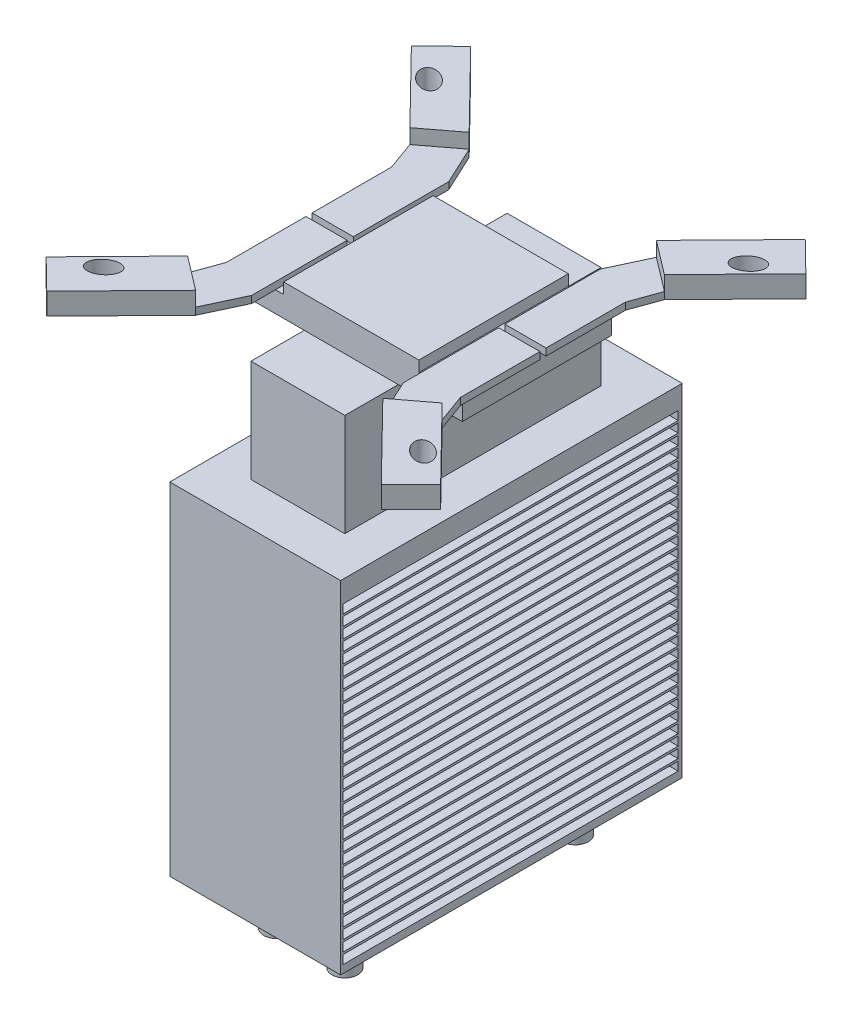
SolidWorks part; units mm, degrees
ref_plane "Front Plane" through (0, 0, 0) normal (0, 0, 1) x (1, 0, 0)
ref_plane "Top Plane" through (0, 0, 0) normal (0, 1, 0) x (1, 0, 0)
ref_plane "Right Plane" through (0, 0, 0) normal (1, 0, 0) x (0, 0, -1)
sketch "Sketch1" plane through (0, 0, 0) normal (0, 1, 0) x (1, 0, 0)
  line L1 (-52.1271, 39.0529) -> (-12.1271, 39.0529)
  line L2 (-52.1271, 39.0529) -> (-52.1271, -40.9471)
  line L3 (-52.1271, -40.9471) -> (-12.1271, -40.9471)
  line L4 (-12.1271, 39.0529) -> (-12.1271, -40.9471)
  dimension "D1" = 40
  dimension "D2" = 80
extrude "Boss-Extrude1" add sketch "Sketch1" along normal blind 80
sketch "Sketch2" plane through (0, 0, 0) normal (0, -1, 0) x (1, 0, 0)
  line L0 (-52.1271, -39.0529) -> (-52.1271, 40.9471) construction
  line L1 (-12.1271, 40.9471) -> (-12.1271, -39.0529) construction
  line L2 (-52.1271, 40.9471) -> (-12.1271, 40.9471) construction
  line L3 (-12.1271, -39.0529) -> (-52.1271, -39.0529) construction
  circle A0 centre (-40.1271, 27.9471) radius 3
  circle A1 centre (-40.1271, -26.0529) radius 3
  circle A2 centre (-24.1271, 27.9471) radius 3
  circle A3 centre (-24.1271, -26.0529) radius 3
  dimension "D1" = 12
  dimension "D2" = 12
  dimension "D3" = 13
  dimension "D4" = 13
  dimension "D5" = 13
  dimension "D6" = 13
  dimension "D7" = 12
  dimension "D8" = 12
extrude "Boss-Extrude2" add sketch "Sketch2" along normal blind 11
sketch "Sketch3" [suppressed] plane through (0, 80, 0) normal (0, 1, 0) x (1, 0, 0)
  line L0 (-12.1271, 39.0529) -> (-52.1271, 39.0529) construction
  line L1 (-52.1271, -40.9471) -> (-12.1271, -40.9471) construction
  line L2 (-52.1271, 39.0529) -> (-52.1271, -40.9471) construction
  line L3 (-12.1271, -40.9471) -> (-12.1271, 39.0529) construction
  circle A0 centre (-40.1271, 26.0529) radius 3
  circle A1 centre (-40.1271, -27.9471) radius 3
  circle A2 centre (-24.1271, 26.0529) radius 3
  circle A3 centre (-24.1271, -27.9471) radius 3
  dimension "D1" = 13
  dimension "D2" = 13
  dimension "D3" = 13
  dimension "D4" = 13
  dimension "D5" = 12
  dimension "D6" = 12
  dimension "D7" = 12
  dimension "D8" = 12
sketch "Sketch7" plane through (0, 80, 0) normal (0, 1, 0) x (1, 0, 0)
  line L1 (-43.1271, 29.0529) -> (-21.1271, 29.0529)
  line L2 (-43.1271, 29.0529) -> (-43.1271, -30.9471)
  line L3 (-43.1271, -30.9471) -> (-21.1271, -30.9471)
  line L4 (-21.1271, 29.0529) -> (-21.1271, -30.9471)
extrude "Boss-Extrude4" add sketch "Sketch7" along normal blind 24
sketch "Sketch8" plane through (0, 104, 0) normal (0, 1, 0) x (1, 0, 0)
  line L1 (-58.1271, 16.5529) -> (-6.1271, 16.5529)
  line L2 (-58.1271, 16.5529) -> (-58.1271, -18.4471)
  line L3 (-58.1271, -18.4471) -> (-6.1271, -18.4471)
  line L4 (-6.1271, 16.5529) -> (-6.1271, -18.4471)
  line L5 (-12.1271, 39.0529) -> (-52.1271, 39.0529) construction
  line L7 (-52.1271, 39.0529) -> (-52.1271, -40.9471) construction
  point P4 (-32.1271, 16.5529)
  point P8 (-58.1271, -0.9471)
  dimension "D1" = 52
  dimension "D2" = 35
  dimension "D3" = 40
  dimension "D4" = 20
extrude "Boss-Extrude5" add sketch "Sketch8" along normal blind 4.86
sketch "Sketch9" plane through (0, 108.86, 0) normal (0, 1, 0) x (1, 0, 0)
  line L0 (-6.1271, 16.5529) -> (-58.1271, 16.5529) construction
  line L1 (-47.9671, 16.5529) -> (-16.2871, 16.5529)
  line L2 (-47.9671, 16.5529) -> (-47.9671, -18.4471)
  line L3 (-47.9671, -18.4471) -> (-16.2871, -18.4471)
  line L4 (-16.2871, 16.5529) -> (-16.2871, -18.4471)
  line L5 (-58.1271, -18.4471) -> (-6.1271, -18.4471) construction
  line L6 (-58.1271, 16.5529) -> (-58.1271, -18.4471) construction
  line L7 (-6.1271, -18.4471) -> (-6.1271, 16.5529) construction
  dimension "D1" = 10.16
  dimension "D2" = 10.16
  dimension "D3" = 31.68
  dimension "D4" = 35
  dimension "D5" = 31.68
extrude "Boss-Extrude6" add sketch "Sketch9" along normal blind 2.54
sketch "Sketch10" plane through (0, 108.86, 0) normal (0, 1, 0) x (1, 0, 0)
  line L0 (-16.2871, -18.4471) -> (-16.2871, 16.5529) construction
  line L1 (-14.3821, -1.6721) -> (-4.7301, -1.6721)
  line L2 (-14.3821, -1.6721) -> (-14.3821, -24.0241)
  line L3 (-47.9671, -0.9471) -> (-67.7333, -0.9471) construction
  line L4 (-4.7301, -1.6721) -> (-4.7301, -20.2903)
  line L5 (-14.3821, -24.0241) -> (-10.2049, -32.9783)
  line L6 (-10.2049, -32.9783) -> (-2.3202, -26.9816)
  line L7 (-4.7301, -20.2903) -> (-2.3202, -26.9816)
  line L8 (-16.2871, -0.9471) -> (3.4792, -0.9471) construction
  line L9 (-32.1271, -16.0781) -> (-32.1271, 19.2692) construction
  line L10 (-16.2871, 16.5529) -> (-47.9671, 16.5529) construction
  line L11 (-14.3821, -0.2221) -> (-4.7301, -0.2221)
  line L12 (-4.7301, -0.2221) -> (-4.7301, 18.3961)
  line L13 (-14.3821, -0.2221) -> (-14.3821, 22.1299)
  line L14 (-4.7301, 18.3961) -> (-2.3202, 25.0873)
  line L15 (-10.2049, 31.084) -> (-2.3202, 25.0873)
  line L17 (-14.3821, 22.1299) -> (-10.2049, 31.084)
  line L18 (-47.9671, 16.5529) -> (-47.9671, -18.4471) construction
  line L19 (-49.8721, 22.1299) -> (-54.0493, 31.084)
  line L21 (-54.0493, 31.084) -> (-61.9339, 25.0873)
  line L22 (-59.5241, 18.3961) -> (-61.9339, 25.0873)
  line L23 (-49.8721, -0.2221) -> (-49.8721, 22.1299)
  line L24 (-59.5241, -0.2221) -> (-59.5241, 18.3961)
  line L25 (-49.8721, -0.2221) -> (-59.5241, -0.2221)
  line L26 (-47.9671, -0.9471) -> (-67.7333, -0.9471) construction
  line L27 (-59.5241, -20.2903) -> (-61.9339, -26.9816)
  line L28 (-54.0493, -32.9783) -> (-61.9339, -26.9816)
  line L29 (-49.8721, -24.0241) -> (-54.0493, -32.9783)
  line L30 (-59.5241, -1.6721) -> (-59.5241, -20.2903)
  line L32 (-49.8721, -1.6721) -> (-49.8721, -24.0241)
  line L33 (-49.8721, -1.6721) -> (-59.5241, -1.6721)
  dimension "D1" = 1.905
  dimension "D2" = 9.906
  dimension "D3" = 9.8806
  dimension "D4" = 7.112
  dimension "D5" = 0.725
  dimension "D6" = 15.84
  dimension "D7" = 18.6182
  dimension "D8" = 22.352
  dimension "D9" = 17.5
  dimension "D10" = 9.652
extrude "Boss-Extrude9" add sketch "Sketch10" along normal blind 1.651 contours L30 L27 L28 L29 L32 L33 | L24 L22 L21 L19 L23 L25 | L13 L17 L15 L14 L12 L11 | L4 L7 L6 L5 L2 L1
sketch "Sketch11" plane through (0, 108.86, 0) normal (0, -1, 0) x (1, 0, 0)
  line L0 (-61.9339, -25.0873) -> (-78.3249, -41.825)
  line L1 (-54.0493, -31.084) -> (-71.3024, -48.7021)
  line L2 (-71.3024, -48.7021) -> (-78.3249, -41.825)
  line L3 (-61.9339, 26.9816) -> (-78.3249, 43.7193)
  line L4 (-54.0493, 32.9783) -> (-71.3024, 50.5964)
  line L5 (-16.2871, 18.4471) -> (-16.2871, -16.5529) construction
  line L6 (-32.1271, -13.8858) -> (-32.1271, 30.975) construction
  line L7 (-16.2871, 0.9471) -> (-1.354, 0.9471) construction
  line L8 (-47.9671, 0.9471) -> (-62.9001, 0.9471) construction
  line L9 (-47.9671, -16.5529) -> (-47.9671, 18.4471) construction
  line L10 (-71.3024, 50.5964) -> (-78.3249, 43.7193)
  line L13 (-16.2871, 0.9471) -> (-1.354, 0.9471) construction
  line L14 (7.0483, 50.5964) -> (14.0708, 43.7193)
  line L15 (-10.2049, 32.9783) -> (7.0483, 50.5964)
  line L16 (-2.3202, 26.9816) -> (14.0708, 43.7193)
  line L17 (7.0483, -48.7021) -> (14.0708, -41.825)
  line L18 (-10.2049, -31.084) -> (7.0483, -48.7021)
  line L19 (-2.3202, -25.0873) -> (14.0708, -41.825)
  line L20 (-61.9339, -25.0873) -> (-54.0493, -31.084)
  line L21 (-61.9339, 26.9816) -> (-54.0493, 32.9783)
  line L22 (-2.3202, 26.9816) -> (-10.2049, 32.9783)
  line L23 (-2.3202, -25.0873) -> (-10.2049, -31.084)
  ellipse E0 centre (-69.5286, -37.1529) end of major axis (-66.8533, -35.0956) minor radius 2.2001
  ellipse E1 centre (-69.5286, 39.0471) end of major axis (-72.2038, 41.1044) minor radius 2.2001
  ellipse E2 centre (5.2744, 39.0471) end of major axis (7.9497, 41.1044) minor radius 2.2001
  ellipse E3 centre (5.2744, -37.1529) end of major axis (7.9497, -39.2101) minor radius 2.2001
  dimension "D1" = 15.84
  dimension "D2" = 76.2
  dimension "D3" = 74.803
extrude "Boss-Extrude10" add sketch "Sketch11" against normal blind 5.08 separate body
sketch "Sketch12" plane through (-12.1271, 0, 0) normal (1, 0, 0) x (0, 0, -1)
  line L0 (-40.3776, 72.4257) -> (38.1108, 72.4257)
  line L1 (-40.3776, 74.9657) -> (38.1108, 74.9657)
  line L2 (-40.3776, 74.9657) -> (-40.3776, 72.9337)
  line L3 (-40.3776, 72.9337) -> (38.1108, 72.9337)
  line L4 (38.1108, 74.9657) -> (38.1108, 72.9337)
  line L5 (-40.3776, 72.4257) -> (-40.3776, 70.3937)
  line L6 (-40.3776, 70.3937) -> (38.1108, 70.3937)
  line L7 (38.1108, 72.4257) -> (38.1108, 70.3937)
  line L8 (-40.3776, 69.8857) -> (38.1108, 69.8857)
  line L9 (-40.3776, 69.8857) -> (-40.3776, 67.8537)
  line L10 (-40.3776, 67.8537) -> (38.1108, 67.8537)
  line L11 (38.1108, 69.8857) -> (38.1108, 67.8537)
  line L12 (-40.3776, 67.3457) -> (38.1108, 67.3457)
  line L13 (-40.3776, 67.3457) -> (-40.3776, 65.3137)
  line L14 (-40.3776, 65.3137) -> (38.1108, 65.3137)
  line L15 (38.1108, 67.3457) -> (38.1108, 65.3137)
  line L16 (-40.3776, 64.8057) -> (38.1108, 64.8057)
  line L17 (-40.3776, 64.8057) -> (-40.3776, 62.7737)
  line L18 (-40.3776, 62.7737) -> (38.1108, 62.7737)
  line L19 (38.1108, 64.8057) -> (38.1108, 62.7737)
  line L20 (-40.3776, 62.2657) -> (38.1108, 62.2657)
  line L21 (-40.3776, 62.2657) -> (-40.3776, 60.2337)
  line L22 (-40.3776, 60.2337) -> (38.1108, 60.2337)
  line L23 (38.1108, 62.2657) -> (38.1108, 60.2337)
  line L24 (-40.3776, 59.7257) -> (38.1108, 59.7257)
  line L25 (-40.3776, 59.7257) -> (-40.3776, 57.6937)
  line L26 (-40.3776, 57.6937) -> (38.1108, 57.6937)
  line L27 (38.1108, 59.7257) -> (38.1108, 57.6937)
  line L28 (-40.3776, 57.1857) -> (38.1108, 57.1857)
  line L29 (-40.3776, 57.1857) -> (-40.3776, 55.1537)
  line L30 (-40.3776, 55.1537) -> (38.1108, 55.1537)
  line L31 (38.1108, 57.1857) -> (38.1108, 55.1537)
  line L32 (-40.3776, 54.6457) -> (38.1108, 54.6457)
  line L33 (-40.3776, 54.6457) -> (-40.3776, 52.6137)
  line L34 (-40.3776, 52.6137) -> (38.1108, 52.6137)
  line L35 (38.1108, 54.6457) -> (38.1108, 52.6137)
  line L36 (-40.3776, 52.1057) -> (38.1108, 52.1057)
  line L37 (-40.3776, 52.1057) -> (-40.3776, 50.0737)
  line L38 (-40.3776, 50.0737) -> (38.1108, 50.0737)
  line L39 (38.1108, 52.1057) -> (38.1108, 50.0737)
  line L40 (-40.3776, 49.5657) -> (38.1108, 49.5657)
  line L41 (-40.3776, 49.5657) -> (-40.3776, 47.5337)
  line L42 (-40.3776, 47.5337) -> (38.1108, 47.5337)
  line L43 (38.1108, 49.5657) -> (38.1108, 47.5337)
  line L44 (-40.3776, 47.0257) -> (38.1108, 47.0257)
  line L45 (-40.3776, 47.0257) -> (-40.3776, 44.9937)
  line L46 (-40.3776, 44.9937) -> (38.1108, 44.9937)
  line L47 (38.1108, 47.0257) -> (38.1108, 44.9937)
  line L48 (-40.3776, 44.4857) -> (38.1108, 44.4857)
  line L49 (-40.3776, 44.4857) -> (-40.3776, 42.4537)
  line L50 (-40.3776, 42.4537) -> (38.1108, 42.4537)
  line L51 (38.1108, 44.4857) -> (38.1108, 42.4537)
  line L52 (-40.3776, 41.9457) -> (38.1108, 41.9457)
  line L53 (-40.3776, 41.9457) -> (-40.3776, 39.9137)
  line L54 (-40.3776, 39.9137) -> (38.1108, 39.9137)
  line L55 (38.1108, 41.9457) -> (38.1108, 39.9137)
  line L56 (-40.3776, 39.4057) -> (38.1108, 39.4057)
  line L57 (-40.3776, 39.4057) -> (-40.3776, 37.3737)
  line L58 (-40.3776, 37.3737) -> (38.1108, 37.3737)
  line L59 (38.1108, 39.4057) -> (38.1108, 37.3737)
  line L60 (-40.3776, 36.8657) -> (38.1108, 36.8657)
  line L61 (-40.3776, 36.8657) -> (-40.3776, 34.8337)
  line L62 (-40.3776, 34.8337) -> (38.1108, 34.8337)
  line L63 (38.1108, 36.8657) -> (38.1108, 34.8337)
  line L64 (-40.3776, 34.3257) -> (38.1108, 34.3257)
  line L65 (-40.3776, 34.3257) -> (-40.3776, 32.2937)
  line L66 (-40.3776, 32.2937) -> (38.1108, 32.2937)
  line L67 (38.1108, 34.3257) -> (38.1108, 32.2937)
  line L68 (-40.3776, 31.7857) -> (38.1108, 31.7857)
  line L69 (-40.3776, 31.7857) -> (-40.3776, 29.7537)
  line L70 (-40.3776, 29.7537) -> (38.1108, 29.7537)
  line L71 (38.1108, 31.7857) -> (38.1108, 29.7537)
  line L72 (-40.3776, 29.2457) -> (38.1108, 29.2457)
  line L73 (-40.3776, 29.2457) -> (-40.3776, 27.2137)
  line L74 (-40.3776, 27.2137) -> (38.1108, 27.2137)
  line L75 (38.1108, 29.2457) -> (38.1108, 27.2137)
  line L76 (-40.3776, 26.7057) -> (38.1108, 26.7057)
  line L77 (-40.3776, 26.7057) -> (-40.3776, 24.6737)
  line L78 (-40.3776, 24.6737) -> (38.1108, 24.6737)
  line L79 (38.1108, 26.7057) -> (38.1108, 24.6737)
  line L80 (-40.3776, 24.1657) -> (38.1108, 24.1657)
  line L81 (-40.3776, 24.1657) -> (-40.3776, 22.1337)
  line L82 (-40.3776, 22.1337) -> (38.1108, 22.1337)
  line L83 (38.1108, 24.1657) -> (38.1108, 22.1337)
  line L84 (-40.3776, 21.6257) -> (38.1108, 21.6257)
  line L85 (-40.3776, 21.6257) -> (-40.3776, 19.5937)
  line L86 (-40.3776, 19.5937) -> (38.1108, 19.5937)
  line L87 (38.1108, 21.6257) -> (38.1108, 19.5937)
  line L88 (-40.3776, 19.0857) -> (38.1108, 19.0857)
  line L89 (-40.3776, 19.0857) -> (-40.3776, 17.0537)
  line L90 (-40.3776, 17.0537) -> (38.1108, 17.0537)
  line L91 (38.1108, 19.0857) -> (38.1108, 17.0537)
  line L92 (-40.3776, 16.5457) -> (38.1108, 16.5457)
  line L93 (-40.3776, 16.5457) -> (-40.3776, 14.5137)
  line L94 (-40.3776, 14.5137) -> (38.1108, 14.5137)
  line L95 (38.1108, 16.5457) -> (38.1108, 14.5137)
  line L96 (-40.3776, 14.0057) -> (38.1108, 14.0057)
  line L97 (-40.3776, 14.0057) -> (-40.3776, 11.9737)
  line L98 (-40.3776, 11.9737) -> (38.1108, 11.9737)
  line L99 (38.1108, 14.0057) -> (38.1108, 11.9737)
  line L100 (-40.3776, 11.4657) -> (38.1108, 11.4657)
  line L101 (-40.3776, 11.4657) -> (-40.3776, 9.4337)
  line L102 (-40.3776, 9.4337) -> (38.1108, 9.4337)
  line L103 (38.1108, 11.4657) -> (38.1108, 9.4337)
  line L104 (-40.3776, 8.9257) -> (38.1108, 8.9257)
  line L105 (-40.3776, 8.9257) -> (-40.3776, 6.8937)
  line L106 (-40.3776, 6.8937) -> (38.1108, 6.8937)
  line L107 (38.1108, 8.9257) -> (38.1108, 6.8937)
  line L108 (-40.3776, 6.3857) -> (38.1108, 6.3857)
  line L109 (-40.3776, 6.3857) -> (-40.3776, 4.3537)
  line L110 (-40.3776, 4.3537) -> (38.1108, 4.3537)
  line L111 (38.1108, 6.3857) -> (38.1108, 4.3537)
  line L112 (-40.3776, 3.8457) -> (38.1108, 3.8457)
  line L113 (-40.3776, 3.8457) -> (-40.3776, 1.8137)
  line L114 (-40.3776, 1.8137) -> (38.1108, 1.8137)
  line L115 (38.1108, 3.8457) -> (38.1108, 1.8137)
  dimension "D1" = 2.032
  dimension "D2" = 29
extrude "Cut-Extrude1" cut sketch "Sketch12" against normal through all
ref_point "Point1"
ref_axis "Axis1" through (5.2744, 108.86, 39.0471) along (0, -1, 0)
equation "\"D3@Sketch8\" = \"D2@Sketch1\"/2"
equation "\"D4@Sketch8\" = \"D1@Sketch1\"/2"
equation "\"D6@Sketch10\" = \"D3@Sketch9\"/2"
equation "\"D9@Sketch10\" =\"D4@Sketch9\"/2"
equation "\"D1@Sketch11\" = \"D3@Sketch9\"/2"
